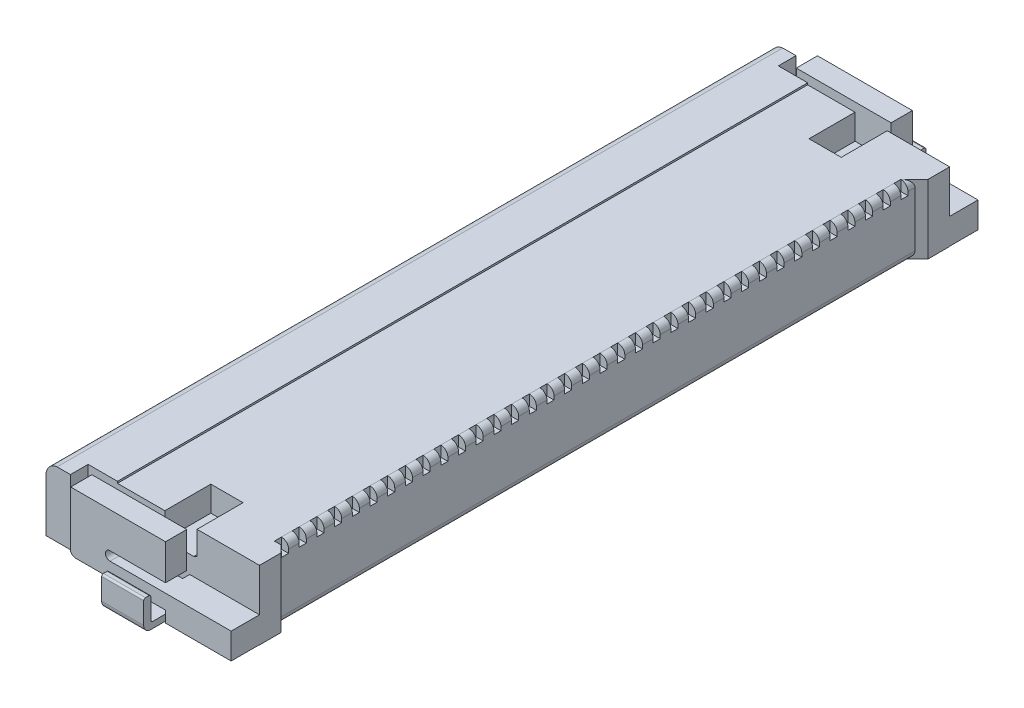
SolidWorks part; units mm, degrees
ref_plane "Front Plane" through (0, 0, 0) normal (0, 0, 1) x (1, 0, 0)
ref_plane "Top Plane" through (0, 0, 0) normal (0, 1, 0) x (1, 0, 0)
ref_plane "Right Plane" through (0, 0, 0) normal (1, 0, 0) x (0, 0, -1)
sketch "Sketch5" plane through (0, 0, 0) normal (0, 0, 1) x (1, 0, 0)
  line L0 (40.6667, 46) -> (203.3333, 46) construction
  line L1 (1.0365, 0.0671) -> (5.5705, 0.0671)
  line L2 (5.5705, 0.0671) -> (5.5705, 2.0592)
  line L3 (5.5705, 2.0592) -> (1.0365, 2.0592)
  line L4 (1.0365, 2.0592) -> (1.0365, 0.0671)
  line L5 (1.0365, 0.9096) -> (0.7294, 0.9096)
  line L6 (0.7294, 0.9096) -> (0.7294, 2.0592)
  line L7 (0.7294, 2.0592) -> (1.0365, 2.0592)
  line L8 (2.4126, 0.8573) -> (2.4126, 0.0671)
  line L9 (2.4126, 0.8573) -> (3.5997, 0.8573)
  line L10 (3.5997, 0.8573) -> (3.5997, 0.0671)
  line L11 (3.5997, 0.7994) -> (5.5705, 0.7994)
  line L12 (2.4126, 0.7994) -> (2.1463, 0.7994)
  line L13 (2.1463, 1.0542) -> (3.7156, 1.0542)
  line L14 (3.7156, 1.0542) -> (3.7156, 2.0592)
  line L15 (2.4126, 0.175) -> (1.0365, 0.175)
  line L16 (3.5997, 0.175) -> (5.5705, 0.175)
  line L17 (2.4126, 0.3858) -> (1.1847, 0.3858)
  line L18 (0.0415, 1.6702) -> (0.0415, 0.2199)
  line L19 (0.0415, 0.2199) -> (0.7294, 0.2199)
  line L20 (0.7294, 0.2199) -> (0.7294, 0.9096)
  line L21 (0.7294, 2.0592) -> (0.3527, 2.0592)
  line L22 (3.8064, 2.0592) -> (3.8064, 1.3482)
  line L23 (3.8064, 1.3482) -> (3.7156, 1.2979)
  line L24 (0.9408, 0.9096) -> (0.9408, 1.2134)
  line L25 (0.9408, 1.2134) -> (1.0365, 1.2134)
  line L26 (3.5997, 0.3858) -> (3.7156, 0.3858)
  line L27 (3.7156, 0.3858) -> (3.7156, 0.175)
  arc A0 (2.1463, 0.7994) -> (2.1463, 1.0542) centre (2.1463, 0.9268) cw
  arc A1 (0.0415, 1.6702) -> (0.3527, 2.0592) centre (0.3916, 1.7091) cw
  spline S0 degree 2 poles (1.1847, 0.3858) (1.082, 0.3886) (1.0365, 0.477) knots 0 0 0 1 1 1
extrude "Boss-Extrude1" add sketch "Sketch5" against normal blind 0.6 contours S0 L17 L8 L12 A0 L13 L14 L3 L4
sketch "Sketch7" plane through (0, 0, 0) normal (0, 0, 1) x (1, 0, 0)
  line L0 (5.5705, 0.0671) -> (5.5705, 2.0592) construction
  line L2 (3.7156, 0.3858) -> (3.7156, 0.175) construction
  line L3 (3.5997, 0.3858) -> (3.7156, 0.3858) construction
  line L4 (3.5997, 0.7994) -> (5.5705, 0.7994) construction
  line L10 (5.5705, 0.175) -> (5.5705, 0.7994)
  line L11 (3.7156, 0.175) -> (3.7156, 0.0671)
  line L12 (3.7156, 0.3858) -> (3.7156, 0.175)
  line L13 (3.5997, 0.3858) -> (3.7156, 0.3858)
  line L14 (3.5997, 0.7994) -> (5.5705, 0.7994)
  line L15 (3.5997, 0.7994) -> (3.5997, 0.3858)
  line L16 (1.0365, 0.0671) -> (5.5705, 0.0671) construction
  line L17 (3.7156, 0.0671) -> (5.5705, 0.0671)
  line L18 (5.5705, 0.0671) -> (5.5705, 0.175)
  line L20 (2.4126, 0.3858) -> (3.5997, 0.3858)
  line L21 (2.4126, 0.7994) -> (3.5997, 0.7994)
  line L24 (2.4126, 0.7994) -> (2.4126, 0.3858)
extrude "Boss-Extrude2" add sketch "Sketch7" against normal blind 0.8 separate body contours L17 L18 L10 L14 L15 L13 L12 L11
sketch "Sketch8" plane through (0, 0, 0) normal (0, 0, 1) x (1, 0, 0)
  line L0 (3.5997, 0.7994) -> (2.4126, 0.7994)
  line L1 (3.5997, 0.3858) -> (2.4126, 0.3858)
  line L2 (3.5997, 0.8573) -> (3.5997, 0.0671) construction
  line L3 (2.4126, 0.8573) -> (2.4126, 0.0671) construction
  line L4 (3.5997, 0.7994) -> (3.5997, 0.3858)
  line L5 (2.4126, 0.7994) -> (2.4126, 0.3858)
extrude "Boss-Extrude3" add sketch "Sketch8" against normal blind 0.6
sketch "Sketch11" plane through (0, 0, 0) normal (0, 1, 0) x (1, 0, 0)
  line L0 (5.5705, 0.8) -> (5.5705, 1.4131)
  line L1 (5.5705, 1.4131) -> (5.3077, 1.5403)
  line L2 (5.3077, 1.5403) -> (5.3077, 9.05)
  line L3 (3.5997, 0) -> (5.5705, 0) construction
  line L4 (5.3077, 9.05) -> (1.7077, 9.05)
  line L5 (1.7077, 9.05) -> (1.7077, 0.8)
  line L6 (1.7077, 0.8) -> (5.5705, 0.8)
  dimension "D1" = 9.05
  dimension "D2" = 3.6
ref_plane "Plane1" through (0, 0.06, 0) normal (0, 1, 0) x (1, 0, 0)
sketch "Sketch13" plane through (0, 0.06, 0) normal (0, 1, 0) x (1, 0, 0)
  line L0 (3.7156, 0) -> (1.0365, 0) construction
  line L2 (5.5705, 0.8) -> (5.5705, 1.4131) construction
  line L6 (5.3077, 10.55) -> (1.6924, 10.55)
  line L7 (5.5705, 1.4131) -> (5.3881, 1.5955)
  line L8 (5.5705, 0.8) -> (5.5705, 1.4131)
  line L9 (1.6924, 10.55) -> (1.6924, 0.8)
  line L10 (5.3881, 1.5955) -> (5.3881, 10.55)
  line L11 (1.6924, 0.8) -> (5.5705, 0.8)
  line L12 (5.3881, 10.55) -> (5.3077, 10.55)
  dimension "D1" = 10.55
extrude "Boss-Extrude5" add sketch "Sketch13" along normal up to surface (1.9992 mm away) up to face at (2.376, 2.0592, -0.3)
sketch "Sketch17" plane through (0, 0, -0.8) normal (0, 0, 1) x (1, 0, 0)
  line L0 (3.8064, 1.3482) -> (3.7156, 1.2979) construction
  line L1 (3.8064, 2.0592) -> (3.8064, 1.3482) construction
  line L2 (3.8064, 1.3482) -> (3.7156, 1.2979)
  line L3 (3.8064, 2.0592) -> (3.8064, 1.3482)
  line L4 (3.7156, 1.2979) -> (2.8963, 1.2979)
  line L5 (2.8963, 1.2979) -> (2.8963, 2.0592)
  line L6 (1.6924, 2.0592) -> (5.5705, 2.0592) construction
  line L7 (2.8963, 2.0592) -> (3.8064, 2.0592)
extrude "Cut-Extrude6" cut sketch "Sketch17" against normal blind 1.3
sketch "Sketch18" plane through (0, 0, -0.8) normal (0, 0, 1) x (1, 0, 0)
  line L0 (0.0415, 1.6702) -> (0.0415, 0.2199)
  line L1 (0.7294, 2.0592) -> (0.7294, 0.9096)
  line L5 (0.0415, 0.2199) -> (0.7294, 0.2199) construction
  line L6 (0.7294, 0.2199) -> (0.7294, 0.9096) construction
  line L9 (0.7294, 2.0592) -> (0.3527, 2.0592) construction
  line L15 (0.0415, 0.2199) -> (0.7294, 0.2199)
  line L16 (0.7294, 0.2199) -> (0.7294, 0.9096)
  line L19 (0.7294, 2.0592) -> (0.3527, 2.0592)
  arc A0 (0.3527, 2.0592) -> (0.0415, 1.6702) centre (0.3916, 1.7091) ccw construction
  arc A1 (0.3527, 2.0592) -> (0.0415, 1.6702) centre (0.3916, 1.7091) ccw
sketch "Sketch19" plane through (1.6924, 0, 0) normal (-1, 0, 0) x (0, 0, 1)
  line L0 (-10.55, 2.0592) -> (-0.8, 2.0592) construction
  line L1 (-10.55, 2.0592) -> (-0.8, 2.0592)
  line L4 (-0.8, 2.0592) -> (-10.55, 2.0592)
  line L5 (-10.55, 2.0592) -> (-10.55, 0.06)
  line L6 (-10.55, 0.06) -> (-0.8, 0.06)
  line L7 (-0.8, 0.06) -> (-0.8, 2.0592)
  line L9 (-10.55, 2.0592) -> (-10.55, 0.06)
  line L10 (-10.55, 0.06) -> (-0.8, 0.06)
  line L11 (-0.8, 0.06) -> (-0.8, 2.0592)
  dimension "D1" = 0
extrude "Boss-Extrude6" add sketch "Sketch19" along normal up to vertex (0.963 mm away) separate body up to point (0.7294, 2.0592, -0.8)
extrude "Boss-Extrude7" add sketch "Sketch18" against normal up to surface (9.75 mm away) up to face at (3.5403, 1.0596, -10.55)
sketch "Sketch20" plane through (0, 0, -0.8) normal (0, 0, 1) x (1, 0, 0)
  line L0 (1.0365, 2.0592) -> (1.0365, 0.0671) construction
  line L1 (0.7294, 0.2199) -> (0.7294, 0.9096) construction
  line L2 (1.0365, 0.9096) -> (0.7294, 0.9096) construction
  line L3 (1.0365, 2.0592) -> (1.0365, 0.0671)
  line L4 (0.7294, 0.2199) -> (0.7294, 0.9096)
  line L5 (1.0365, 0.9096) -> (0.7294, 0.9096)
  line L6 (0.7294, 0.2199) -> (0.7294, 0.06)
  line L7 (0.7294, -0.0203) -> (1.0365, -0.0203)
  line L8 (1.0365, -0.0203) -> (1.0365, 0.0671)
  line L9 (0.7294, 0.06) -> (0.7294, -0.0203)
extrude "Cut-Extrude7" cut sketch "Sketch20" against normal up to surface (9.75 mm away)
sketch "Sketch21" plane through (0, 0, -0.8) normal (0, 0, 1) x (1, 0, 0)
  line L0 (0.7294, 0.2199) -> (0.7294, 0.9096) construction
  line L1 (0.0415, 0.2199) -> (0.7294, 0.2199) construction
  line L2 (0.0415, 1.6702) -> (0.0415, 0.2199) construction
  line L3 (0.7294, 2.0592) -> (0.3527, 2.0592) construction
  line L4 (0.7294, 0.9096) -> (0.7294, 2.0592) construction
  line L5 (0.7294, 0.2199) -> (0.7294, 0.9096)
  line L6 (0.0415, 0.2199) -> (0.7294, 0.2199)
  line L7 (0.0415, 1.6702) -> (0.0415, 0.2199)
  line L8 (0.7294, 2.0592) -> (0.3527, 2.0592)
  line L9 (0.7294, 0.9096) -> (0.7294, 2.0592)
  arc A0 (0.3527, 2.0592) -> (0.0415, 1.6702) centre (0.3916, 1.7091) ccw construction
  arc A1 (0.3527, 2.0592) -> (0.0415, 1.6702) centre (0.3916, 1.7091) ccw
extrude "Boss-Extrude8" add sketch "Sketch21" along normal blind 0.5
mirror "Mirror1" of "Boss-Extrude8", "Cut-Extrude7", "Boss-Extrude7", "Boss-Extrude6", "Cut-Extrude6", "Boss-Extrude5", "Boss-Extrude3", "Boss-Extrude2", "Boss-Extrude1"
sketch "Sketch22" plane through (0, 2.0592, 0) normal (0, 1, 0) x (1, 0, 0)
  line L0 (1.5582, 20.3) -> (1.5582, 0.8)
  line L20 (2.8963, 19) -> (2.8963, 20.3)
  line L21 (2.8963, 20.3) -> (0.7294, 20.3)
  line L22 (0.7294, 20.3) -> (0.7294, 20.8)
  line L23 (0.7294, 20.8) -> (0.3527, 20.8)
  line L24 (0.3527, 20.8) -> (0.3527, 0.3)
  line L25 (0.3527, 0.3) -> (0.7294, 0.3)
  line L26 (0.7294, 0.3) -> (0.7294, 0.8)
  line L27 (0.7294, 0.8) -> (2.8963, 0.8)
  line L28 (2.8963, 0.8) -> (2.8963, 2.1)
  line L29 (2.8963, 2.1) -> (3.8064, 2.1)
  line L30 (3.8064, 2.1) -> (3.8064, 0.8)
  line L31 (3.8064, 0.8) -> (5.5705, 0.8)
  line L32 (5.5705, 0.8) -> (5.5705, 1.4131)
  line L33 (5.5705, 1.4131) -> (5.3881, 1.5955)
  line L34 (5.5705, 1.4131) -> (5.3881, 1.5955)
  line L35 (5.3881, 1.5955) -> (5.3881, 19.5045)
  line L36 (5.5705, 19.6869) -> (5.5705, 20.3)
  line L37 (5.5705, 20.3) -> (3.8064, 20.3)
  line L38 (3.8064, 20.3) -> (3.8064, 19)
  line L39 (3.8064, 19) -> (2.8963, 19)
  line L40 (2.8963, 19) -> (2.8963, 20.3)
  line L41 (2.8963, 20.3) -> (1.5582, 20.3)
  line L43 (5.3881, 1.5955) -> (5.3881, 19.5045)
  line L44 (5.3881, 19.5045) -> (5.5705, 19.6869)
  line L45 (5.3881, 19.5045) -> (5.5705, 19.6869)
  line L46 (0.7294, 0.3) -> (0.7294, 0.8)
  line L47 (1.5582, 0.8) -> (2.8963, 0.8)
  line L48 (2.8963, 0.8) -> (2.8963, 2.1)
  line L49 (2.8963, 2.1) -> (3.8064, 2.1)
  line L50 (3.8064, 2.1) -> (3.8064, 0.8)
  line L51 (3.8064, 0.8) -> (5.5705, 0.8)
  line L52 (5.5705, 0.8) -> (5.5705, 1.4131)
  line L56 (5.5705, 19.6869) -> (5.5705, 20.3)
  line L57 (5.5705, 20.3) -> (3.8064, 20.3)
  line L58 (3.8064, 20.3) -> (3.8064, 19)
  line L59 (3.8064, 19) -> (2.8963, 19)
  dimension "D1" = 0
extrude "Cut-Extrude8" cut sketch "Sketch22" against normal blind 0.05
fillet "Fillet4" radius 0.2 2 edges at (5.3881, 2.0092, -10.55) (5.3881, 0.06, -10.55)
sketch "Sketch26" plane through (0, 0, 0) normal (0, 0, 1) x (1, 0, 0)
  line L1 (3.5997, 0.8573) -> (3.5997, 0.0671) construction
  line L2 (2.4126, 0.8573) -> (2.4126, 0.0671) construction
  line L3 (2.4126, 0.8573) -> (3.5997, 0.8573) construction
  line L4 (2.4126, 0.0671) -> (2.4126, 0)
  line L5 (3.5997, 0.8573) -> (3.5997, 0.0671)
  line L6 (2.4126, 0.8573) -> (2.4126, 0.0671)
  line L7 (2.4126, 0.8573) -> (3.5997, 0.8573)
  line L8 (2.4126, 0) -> (3.5997, 0)
  line L9 (3.5997, 0) -> (3.5997, 0.0671)
  line L10 (2.4126, 0.175) -> (3.5997, 0.175)
extrude "Boss-Extrude9" add sketch "Sketch26" along normal blind 0.5 contours L10 L6 L4 L8 L9 L5
sketch "Sketch27" plane through (0, 0, 0.5) normal (0, 0, 1) x (1, 0, 0)
  line L0 (2.4126, 0.175) -> (3.5997, 0.175) construction
  line L1 (3.5997, 0.8573) -> (3.5997, 0.0671) construction
  line L2 (2.4126, 0.8573) -> (2.4126, 0.0671) construction
  line L3 (2.4126, 0.8573) -> (3.5997, 0.8573) construction
  line L4 (2.4126, 0.175) -> (3.5997, 0.175)
  line L5 (3.5997, 0.8573) -> (3.5997, 0.175)
  line L6 (2.4126, 0.8573) -> (2.4126, 0.175)
  line L7 (2.4126, 0.8573) -> (3.5997, 0.8573)
extrude "Boss-Extrude10" add sketch "Sketch27" against normal blind 0.2
fillet "Fillet6" radius 0.2 1 edges at (3.0062, 0, 0.5)
fillet "Fillet7" radius 0.05 2 edges at (3.0062, 0.8573, 0.5) (3.0062, 0.8573, 0.3)
sketch "Sketch28" plane through (2.4126, 0, 0) normal (-1, 0, 0) x (0, 0, 1)
  line L0 (-0.8, 0.3858) -> (-0.8, 0.0671) construction
  line L1 (-0.8, 0.3233) -> (-0.8, 0.1393)
  line L2 (0, 0.175) -> (-0.5527, 0.175)
  line L3 (0, 0) -> (-0.5527, 0)
  line L4 (0, 0.175) -> (0, 0)
  arc A0 (-0.5527, 0) -> (-0.8, 0.1393) centre (-0.5056, 0.3729) cw
  arc A1 (-0.5527, 0.175) -> (-0.8, 0.3233) centre (-0.4668, 0.5985) cw
extrude "Boss-Extrude11" add sketch "Sketch28" against normal up to surface (1.1871 mm away) up to face at (3.5997, 0.4287, 0.3046)
ref_plane "Plane3" through (0, 0, -10.55) normal (0, 0, 1) x (1, 0, 0)
mirror "Mirror6" about plane through (0, 0, -10.55) normal (0, 0, 1) of "Boss-Extrude11", "Fillet7", "Fillet6", "Boss-Extrude10", "Boss-Extrude9"
fillet "Fillet8" radius 0.05 1 edges at (3.0062, 0.175, 0.3)
fillet "Fillet9" radius 0.05 1 edges at (3.0062, 0.175, -21.4)
sketch "Sketch29" plane through (0, 2.0092, 0) normal (0, 1, 0) x (1, 0, 0)
  line L0 (6.2655, 18.8045) -> (6.2655, 18.6045)
  line L1 (5.1881, 19.3045) -> (6.2655, 19.3045)
  line L2 (5.1881, 19.3045) -> (5.1881, 19.1045)
  line L3 (5.1881, 19.1045) -> (6.2655, 19.1045)
  line L4 (6.2655, 19.3045) -> (6.2655, 19.1045)
  line L5 (5.1881, 18.8045) -> (6.2655, 18.8045)
  line L6 (5.1881, 18.6045) -> (6.2655, 18.6045)
  line L7 (5.1881, 18.8045) -> (5.1881, 18.6045)
  line L8 (6.2655, 18.3045) -> (6.2655, 18.1045)
  line L9 (5.1881, 18.3045) -> (6.2655, 18.3045)
  line L10 (5.1881, 18.1045) -> (6.2655, 18.1045)
  line L11 (5.1881, 18.3045) -> (5.1881, 18.1045)
  line L12 (6.2655, 17.8045) -> (6.2655, 17.6045)
  line L13 (5.1881, 17.8045) -> (6.2655, 17.8045)
  line L14 (5.1881, 17.6045) -> (6.2655, 17.6045)
  line L15 (5.1881, 17.8045) -> (5.1881, 17.6045)
  line L16 (6.2655, 17.3045) -> (6.2655, 17.1045)
  line L17 (5.1881, 17.3045) -> (6.2655, 17.3045)
  line L18 (5.1881, 17.1045) -> (6.2655, 17.1045)
  line L19 (5.1881, 17.3045) -> (5.1881, 17.1045)
  line L20 (6.2655, 16.8045) -> (6.2655, 16.6045)
  line L21 (5.1881, 16.8045) -> (6.2655, 16.8045)
  line L22 (5.1881, 16.6045) -> (6.2655, 16.6045)
  line L23 (5.1881, 16.8045) -> (5.1881, 16.6045)
  line L24 (6.2655, 16.3045) -> (6.2655, 16.1045)
  line L25 (5.1881, 16.3045) -> (6.2655, 16.3045)
  line L26 (5.1881, 16.1045) -> (6.2655, 16.1045)
  line L27 (5.1881, 16.3045) -> (5.1881, 16.1045)
  line L28 (6.2655, 15.8045) -> (6.2655, 15.6045)
  line L29 (5.1881, 15.8045) -> (6.2655, 15.8045)
  line L30 (5.1881, 15.6045) -> (6.2655, 15.6045)
  line L31 (5.1881, 15.8045) -> (5.1881, 15.6045)
  line L32 (6.2655, 15.3045) -> (6.2655, 15.1045)
  line L33 (5.1881, 15.3045) -> (6.2655, 15.3045)
  line L34 (5.1881, 15.1045) -> (6.2655, 15.1045)
  line L35 (5.1881, 15.3045) -> (5.1881, 15.1045)
  line L36 (6.2655, 14.8045) -> (6.2655, 14.6045)
  line L37 (5.1881, 14.8045) -> (6.2655, 14.8045)
  line L38 (5.1881, 14.6045) -> (6.2655, 14.6045)
  line L39 (5.1881, 14.8045) -> (5.1881, 14.6045)
  line L40 (6.2655, 14.3045) -> (6.2655, 14.1045)
  line L41 (5.1881, 14.3045) -> (6.2655, 14.3045)
  line L42 (5.1881, 14.1045) -> (6.2655, 14.1045)
  line L43 (5.1881, 14.3045) -> (5.1881, 14.1045)
  line L44 (6.2655, 13.8045) -> (6.2655, 13.6045)
  line L45 (5.1881, 13.8045) -> (6.2655, 13.8045)
  line L46 (5.1881, 13.6045) -> (6.2655, 13.6045)
  line L47 (5.1881, 13.8045) -> (5.1881, 13.6045)
  line L48 (6.2655, 13.3045) -> (6.2655, 13.1045)
  line L49 (5.1881, 13.3045) -> (6.2655, 13.3045)
  line L50 (5.1881, 13.1045) -> (6.2655, 13.1045)
  line L51 (5.1881, 13.3045) -> (5.1881, 13.1045)
  line L52 (6.2655, 12.8045) -> (6.2655, 12.6045)
  line L53 (5.1881, 12.8045) -> (6.2655, 12.8045)
  line L54 (5.1881, 12.6045) -> (6.2655, 12.6045)
  line L55 (5.1881, 12.8045) -> (5.1881, 12.6045)
  line L56 (6.2655, 12.3045) -> (6.2655, 12.1045)
  line L57 (5.1881, 12.3045) -> (6.2655, 12.3045)
  line L58 (5.1881, 12.1045) -> (6.2655, 12.1045)
  line L59 (5.1881, 12.3045) -> (5.1881, 12.1045)
  line L60 (6.2655, 11.8045) -> (6.2655, 11.6045)
  line L61 (5.1881, 11.8045) -> (6.2655, 11.8045)
  line L62 (5.1881, 11.6045) -> (6.2655, 11.6045)
  line L63 (5.1881, 11.8045) -> (5.1881, 11.6045)
  line L64 (6.2655, 11.3045) -> (6.2655, 11.1045)
  line L65 (5.1881, 11.3045) -> (6.2655, 11.3045)
  line L66 (5.1881, 11.1045) -> (6.2655, 11.1045)
  line L67 (5.1881, 11.3045) -> (5.1881, 11.1045)
  line L68 (6.2655, 10.8045) -> (6.2655, 10.6045)
  line L69 (5.1881, 10.8045) -> (6.2655, 10.8045)
  line L70 (5.1881, 10.6045) -> (6.2655, 10.6045)
  line L71 (5.1881, 10.8045) -> (5.1881, 10.6045)
  line L72 (6.2655, 10.3045) -> (6.2655, 10.1045)
  line L73 (5.1881, 10.3045) -> (6.2655, 10.3045)
  line L74 (5.1881, 10.1045) -> (6.2655, 10.1045)
  line L75 (5.1881, 10.3045) -> (5.1881, 10.1045)
  line L76 (6.2655, 9.8045) -> (6.2655, 9.6045)
  line L77 (5.1881, 9.8045) -> (6.2655, 9.8045)
  line L78 (5.1881, 9.6045) -> (6.2655, 9.6045)
  line L79 (5.1881, 9.8045) -> (5.1881, 9.6045)
  line L80 (6.2655, 9.3045) -> (6.2655, 9.1045)
  line L81 (5.1881, 9.3045) -> (6.2655, 9.3045)
  line L82 (5.1881, 9.1045) -> (6.2655, 9.1045)
  line L83 (5.1881, 9.3045) -> (5.1881, 9.1045)
  line L84 (6.2655, 8.8045) -> (6.2655, 8.6045)
  line L85 (5.1881, 8.8045) -> (6.2655, 8.8045)
  line L86 (5.1881, 8.6045) -> (6.2655, 8.6045)
  line L87 (5.1881, 8.8045) -> (5.1881, 8.6045)
  line L88 (6.2655, 8.3045) -> (6.2655, 8.1045)
  line L89 (5.1881, 8.3045) -> (6.2655, 8.3045)
  line L90 (5.1881, 8.1045) -> (6.2655, 8.1045)
  line L91 (5.1881, 8.3045) -> (5.1881, 8.1045)
  line L92 (6.2655, 7.8045) -> (6.2655, 7.6045)
  line L93 (5.1881, 7.8045) -> (6.2655, 7.8045)
  line L94 (5.1881, 7.6045) -> (6.2655, 7.6045)
  line L95 (5.1881, 7.8045) -> (5.1881, 7.6045)
  line L96 (6.2655, 7.3045) -> (6.2655, 7.1045)
  line L97 (5.1881, 7.3045) -> (6.2655, 7.3045)
  line L98 (5.1881, 7.1045) -> (6.2655, 7.1045)
  line L99 (5.1881, 7.3045) -> (5.1881, 7.1045)
  line L100 (6.2655, 6.8045) -> (6.2655, 6.6045)
  line L101 (5.1881, 6.8045) -> (6.2655, 6.8045)
  line L102 (5.1881, 6.6045) -> (6.2655, 6.6045)
  line L103 (5.1881, 6.8045) -> (5.1881, 6.6045)
  line L104 (6.2655, 6.3045) -> (6.2655, 6.1045)
  line L105 (5.1881, 6.3045) -> (6.2655, 6.3045)
  line L106 (5.1881, 6.1045) -> (6.2655, 6.1045)
  line L107 (5.1881, 6.3045) -> (5.1881, 6.1045)
  line L108 (6.2655, 5.8045) -> (6.2655, 5.6045)
  line L109 (5.1881, 5.8045) -> (6.2655, 5.8045)
  line L110 (5.1881, 5.6045) -> (6.2655, 5.6045)
  line L111 (5.1881, 5.8045) -> (5.1881, 5.6045)
  line L112 (6.2655, 5.3045) -> (6.2655, 5.1045)
  line L113 (5.1881, 5.3045) -> (6.2655, 5.3045)
  line L114 (5.1881, 5.1045) -> (6.2655, 5.1045)
  line L115 (5.1881, 5.3045) -> (5.1881, 5.1045)
  line L116 (6.2655, 4.8045) -> (6.2655, 4.6045)
  line L117 (5.1881, 4.8045) -> (6.2655, 4.8045)
  line L118 (5.1881, 4.6045) -> (6.2655, 4.6045)
  line L119 (5.1881, 4.8045) -> (5.1881, 4.6045)
  line L120 (6.2655, 4.3045) -> (6.2655, 4.1045)
  line L121 (5.1881, 4.3045) -> (6.2655, 4.3045)
  line L122 (5.1881, 4.1045) -> (6.2655, 4.1045)
  line L123 (5.1881, 4.3045) -> (5.1881, 4.1045)
  line L124 (6.2655, 3.8045) -> (6.2655, 3.6045)
  line L125 (5.1881, 3.8045) -> (6.2655, 3.8045)
  line L126 (5.1881, 3.6045) -> (6.2655, 3.6045)
  line L127 (5.1881, 3.8045) -> (5.1881, 3.6045)
  line L128 (6.2655, 3.3045) -> (6.2655, 3.1045)
  line L129 (5.1881, 3.3045) -> (6.2655, 3.3045)
  line L130 (5.1881, 3.1045) -> (6.2655, 3.1045)
  line L131 (5.1881, 3.3045) -> (5.1881, 3.1045)
  line L132 (6.2655, 2.8045) -> (6.2655, 2.6045)
  line L133 (5.1881, 2.8045) -> (6.2655, 2.8045)
  line L134 (5.1881, 2.6045) -> (6.2655, 2.6045)
  line L135 (5.1881, 2.8045) -> (5.1881, 2.6045)
  line L136 (6.2655, 2.3045) -> (6.2655, 2.1045)
  line L137 (5.1881, 2.3045) -> (6.2655, 2.3045)
  line L138 (5.1881, 2.1045) -> (6.2655, 2.1045)
  line L139 (5.1881, 2.3045) -> (5.1881, 2.1045)
  line L140 (6.2655, 1.8045) -> (6.2655, 1.6045)
  line L141 (5.1881, 1.8045) -> (6.2655, 1.8045)
  line L142 (5.1881, 1.6045) -> (6.2655, 1.6045)
  line L143 (5.1881, 1.8045) -> (5.1881, 1.6045)
  dimension "D1" = 0.2
  dimension "D2" = 36
extrude "Cut-Extrude9" cut sketch "Sketch29" against normal blind 0.3
sketch "Sketch30" plane through (0.0415, 0, 0) normal (-1, 0, 0) x (0, 0, 1)
  line L0 (-19.835, 0.2199) -> (-19.835, 0.9096)
  line L1 (-20.8, 0.2199) -> (-0.3, 0.2199) construction
  line L2 (-19.835, 0.9096) -> (-18.505, 0.9096)
  line L3 (-18.505, 0.9096) -> (-18.505, 1.2296)
  line L4 (-18.505, 1.2296) -> (-2.595, 1.2296)
  line L5 (-10.55, 5.4524) -> (-10.55, -3.5074) construction
  line L6 (-20.3, 0.9096) -> (-0.8, 0.9096) construction
  line L7 (-19.835, 0.9096) -> (-18.505, 0.9096)
  line L8 (-1.265, 0.2199) -> (-1.265, 0.9096)
  line L9 (-1.265, 0.9096) -> (-2.595, 0.9096)
  line L10 (-2.595, 0.9096) -> (-2.595, 1.2296)
  line L11 (-19.835, 0.2199) -> (-1.265, 0.2199)
  point P15 (-10.55, 1.2296)
  line M7 (-20.8, 0.2199) -> (-0.3, 0.2199)
  dimension "D1" = 9.285
  dimension "D2" = 1.33
  dimension "D3" = 0.32
extrude "Cut-Extrude10" cut sketch "Sketch30" against normal up to surface (0.688 mm away) contours L5 L4 L3 L2 L0 M7 | L4 L5 L11 L8 L9 L10 up to face at (0.7294, 1.312, -10.55)
sketch "Sketch31" plane through (1.0365, 0, 0) normal (-1, 0, 0) x (0, 0, 1)
  line L0 (-20.3, 0.9096) -> (-0.8, 0.9096) construction
  line L1 (-19.385, 0.9096) -> (-19.185, 0.9096)
  line L2 (-19.835, 0.2199) -> (-19.835, 0.9096) construction
  line L3 (-19.385, 0.9096) -> (-19.185, 0.9096)
  line L4 (-19.385, 0.9096) -> (-19.385, 0.3696)
  line L5 (-19.385, 0.3696) -> (-19.185, 0.3696)
  line L6 (-19.185, 0.9096) -> (-19.185, 0.3696)
  line L7 (-18.885, 0.9096) -> (-18.685, 0.9096)
  line L8 (-18.685, 0.9096) -> (-18.685, 0.3696)
  line L9 (-18.885, 0.9096) -> (-18.885, 0.3696)
  line L10 (-18.885, 0.3696) -> (-18.685, 0.3696)
  line L11 (-18.385, 0.9096) -> (-18.185, 0.9096)
  line L12 (-18.185, 0.9096) -> (-18.185, 0.3696)
  line L13 (-18.385, 0.9096) -> (-18.385, 0.3696)
  line L14 (-18.385, 0.3696) -> (-18.185, 0.3696)
  line L15 (-17.885, 0.9096) -> (-17.685, 0.9096)
  line L16 (-17.685, 0.9096) -> (-17.685, 0.3696)
  line L17 (-17.885, 0.9096) -> (-17.885, 0.3696)
  line L18 (-17.885, 0.3696) -> (-17.685, 0.3696)
  line L19 (-17.385, 0.9096) -> (-17.185, 0.9096)
  line L20 (-17.185, 0.9096) -> (-17.185, 0.3696)
  line L21 (-17.385, 0.9096) -> (-17.385, 0.3696)
  line L22 (-17.385, 0.3696) -> (-17.185, 0.3696)
  line L23 (-16.885, 0.9096) -> (-16.685, 0.9096)
  line L24 (-16.685, 0.9096) -> (-16.685, 0.3696)
  line L25 (-16.885, 0.9096) -> (-16.885, 0.3696)
  line L26 (-16.885, 0.3696) -> (-16.685, 0.3696)
  line L27 (-16.385, 0.9096) -> (-16.185, 0.9096)
  line L28 (-16.185, 0.9096) -> (-16.185, 0.3696)
  line L29 (-16.385, 0.9096) -> (-16.385, 0.3696)
  line L30 (-16.385, 0.3696) -> (-16.185, 0.3696)
  line L31 (-15.885, 0.9096) -> (-15.685, 0.9096)
  line L32 (-15.685, 0.9096) -> (-15.685, 0.3696)
  line L33 (-15.885, 0.9096) -> (-15.885, 0.3696)
  line L34 (-15.885, 0.3696) -> (-15.685, 0.3696)
  line L35 (-15.385, 0.9096) -> (-15.185, 0.9096)
  line L36 (-15.185, 0.9096) -> (-15.185, 0.3696)
  line L37 (-15.385, 0.9096) -> (-15.385, 0.3696)
  line L38 (-15.385, 0.3696) -> (-15.185, 0.3696)
  line L39 (-14.885, 0.9096) -> (-14.685, 0.9096)
  line L40 (-14.685, 0.9096) -> (-14.685, 0.3696)
  line L41 (-14.885, 0.9096) -> (-14.885, 0.3696)
  line L42 (-14.885, 0.3696) -> (-14.685, 0.3696)
  line L43 (-14.385, 0.9096) -> (-14.185, 0.9096)
  line L44 (-14.185, 0.9096) -> (-14.185, 0.3696)
  line L45 (-14.385, 0.9096) -> (-14.385, 0.3696)
  line L46 (-14.385, 0.3696) -> (-14.185, 0.3696)
  line L47 (-13.885, 0.9096) -> (-13.685, 0.9096)
  line L48 (-13.685, 0.9096) -> (-13.685, 0.3696)
  line L49 (-13.885, 0.9096) -> (-13.885, 0.3696)
  line L50 (-13.885, 0.3696) -> (-13.685, 0.3696)
  line L51 (-13.385, 0.9096) -> (-13.185, 0.9096)
  line L52 (-13.185, 0.9096) -> (-13.185, 0.3696)
  line L53 (-13.385, 0.9096) -> (-13.385, 0.3696)
  line L54 (-13.385, 0.3696) -> (-13.185, 0.3696)
  line L55 (-12.885, 0.9096) -> (-12.685, 0.9096)
  line L56 (-12.685, 0.9096) -> (-12.685, 0.3696)
  line L57 (-12.885, 0.9096) -> (-12.885, 0.3696)
  line L58 (-12.885, 0.3696) -> (-12.685, 0.3696)
  line L59 (-12.385, 0.9096) -> (-12.185, 0.9096)
  line L60 (-12.185, 0.9096) -> (-12.185, 0.3696)
  line L61 (-12.385, 0.9096) -> (-12.385, 0.3696)
  line L62 (-12.385, 0.3696) -> (-12.185, 0.3696)
  line L63 (-11.885, 0.9096) -> (-11.685, 0.9096)
  line L64 (-11.685, 0.9096) -> (-11.685, 0.3696)
  line L65 (-11.885, 0.9096) -> (-11.885, 0.3696)
  line L66 (-11.885, 0.3696) -> (-11.685, 0.3696)
  line L67 (-11.385, 0.9096) -> (-11.185, 0.9096)
  line L68 (-11.185, 0.9096) -> (-11.185, 0.3696)
  line L69 (-11.385, 0.9096) -> (-11.385, 0.3696)
  line L70 (-11.385, 0.3696) -> (-11.185, 0.3696)
  line L71 (-10.885, 0.9096) -> (-10.685, 0.9096)
  line L72 (-10.685, 0.9096) -> (-10.685, 0.3696)
  line L73 (-10.885, 0.9096) -> (-10.885, 0.3696)
  line L74 (-10.885, 0.3696) -> (-10.685, 0.3696)
  line L75 (-10.385, 0.9096) -> (-10.185, 0.9096)
  line L76 (-10.185, 0.9096) -> (-10.185, 0.3696)
  line L77 (-10.385, 0.9096) -> (-10.385, 0.3696)
  line L78 (-10.385, 0.3696) -> (-10.185, 0.3696)
  line L79 (-9.885, 0.9096) -> (-9.685, 0.9096)
  line L80 (-9.685, 0.9096) -> (-9.685, 0.3696)
  line L81 (-9.885, 0.9096) -> (-9.885, 0.3696)
  line L82 (-9.885, 0.3696) -> (-9.685, 0.3696)
  line L83 (-9.385, 0.9096) -> (-9.185, 0.9096)
  line L84 (-9.185, 0.9096) -> (-9.185, 0.3696)
  line L85 (-9.385, 0.9096) -> (-9.385, 0.3696)
  line L86 (-9.385, 0.3696) -> (-9.185, 0.3696)
  line L87 (-8.885, 0.9096) -> (-8.685, 0.9096)
  line L88 (-8.685, 0.9096) -> (-8.685, 0.3696)
  line L89 (-8.885, 0.9096) -> (-8.885, 0.3696)
  line L90 (-8.885, 0.3696) -> (-8.685, 0.3696)
  line L91 (-8.385, 0.9096) -> (-8.185, 0.9096)
  line L92 (-8.185, 0.9096) -> (-8.185, 0.3696)
  line L93 (-8.385, 0.9096) -> (-8.385, 0.3696)
  line L94 (-8.385, 0.3696) -> (-8.185, 0.3696)
  line L95 (-7.885, 0.9096) -> (-7.685, 0.9096)
  line L96 (-7.685, 0.9096) -> (-7.685, 0.3696)
  line L97 (-7.885, 0.9096) -> (-7.885, 0.3696)
  line L98 (-7.885, 0.3696) -> (-7.685, 0.3696)
  line L99 (-7.385, 0.9096) -> (-7.185, 0.9096)
  line L100 (-7.185, 0.9096) -> (-7.185, 0.3696)
  line L101 (-7.385, 0.9096) -> (-7.385, 0.3696)
  line L102 (-7.385, 0.3696) -> (-7.185, 0.3696)
  line L103 (-6.885, 0.9096) -> (-6.685, 0.9096)
  line L104 (-6.685, 0.9096) -> (-6.685, 0.3696)
  line L105 (-6.885, 0.9096) -> (-6.885, 0.3696)
  line L106 (-6.885, 0.3696) -> (-6.685, 0.3696)
  line L107 (-6.385, 0.9096) -> (-6.185, 0.9096)
  line L108 (-6.185, 0.9096) -> (-6.185, 0.3696)
  line L109 (-6.385, 0.9096) -> (-6.385, 0.3696)
  line L110 (-6.385, 0.3696) -> (-6.185, 0.3696)
  line L111 (-5.885, 0.9096) -> (-5.685, 0.9096)
  line L112 (-5.685, 0.9096) -> (-5.685, 0.3696)
  line L113 (-5.885, 0.9096) -> (-5.885, 0.3696)
  line L114 (-5.885, 0.3696) -> (-5.685, 0.3696)
  line L115 (-5.385, 0.9096) -> (-5.185, 0.9096)
  line L116 (-5.185, 0.9096) -> (-5.185, 0.3696)
  line L117 (-5.385, 0.9096) -> (-5.385, 0.3696)
  line L118 (-5.385, 0.3696) -> (-5.185, 0.3696)
  line L119 (-4.885, 0.9096) -> (-4.685, 0.9096)
  line L120 (-4.685, 0.9096) -> (-4.685, 0.3696)
  line L121 (-4.885, 0.9096) -> (-4.885, 0.3696)
  line L122 (-4.885, 0.3696) -> (-4.685, 0.3696)
  line L123 (-4.385, 0.9096) -> (-4.185, 0.9096)
  line L124 (-4.185, 0.9096) -> (-4.185, 0.3696)
  line L125 (-4.385, 0.9096) -> (-4.385, 0.3696)
  line L126 (-4.385, 0.3696) -> (-4.185, 0.3696)
  line L127 (-3.885, 0.9096) -> (-3.685, 0.9096)
  line L128 (-3.685, 0.9096) -> (-3.685, 0.3696)
  line L129 (-3.885, 0.9096) -> (-3.885, 0.3696)
  line L130 (-3.885, 0.3696) -> (-3.685, 0.3696)
  line L131 (-3.385, 0.9096) -> (-3.185, 0.9096)
  line L132 (-3.185, 0.9096) -> (-3.185, 0.3696)
  line L133 (-3.385, 0.9096) -> (-3.385, 0.3696)
  line L134 (-3.385, 0.3696) -> (-3.185, 0.3696)
  line L135 (-2.885, 0.9096) -> (-2.685, 0.9096)
  line L136 (-2.685, 0.9096) -> (-2.685, 0.3696)
  line L137 (-2.885, 0.9096) -> (-2.885, 0.3696)
  line L138 (-2.885, 0.3696) -> (-2.685, 0.3696)
  line L139 (-2.385, 0.9096) -> (-2.185, 0.9096)
  line L140 (-2.185, 0.9096) -> (-2.185, 0.3696)
  line L141 (-2.385, 0.9096) -> (-2.385, 0.3696)
  line L142 (-2.385, 0.3696) -> (-2.185, 0.3696)
  line L143 (-1.885, 0.9096) -> (-1.685, 0.9096)
  line L144 (-1.685, 0.9096) -> (-1.685, 0.3696)
  line L145 (-1.885, 0.9096) -> (-1.885, 0.3696)
  line L146 (-1.885, 0.3696) -> (-1.685, 0.3696)
  line M7 (-0.8, 0.9096) -> (-20.3, 0.9096)
  dimension "D1" = 0.2
  dimension "D2" = 0.54
  dimension "D3" = 0.45
  dimension "D4" = 36
extrude "Boss-Extrude12" add sketch "Sketch31" along normal blind 0.05 contours L6 L4 L5 M7 | L9 L10 L8 M7 | L13 L14 L12 M7 | L17 L18 L16 M7 | L21 L22 L20 M7 | L25 L26 L24 M7 | L33 L34 L32 M7 | L37 L38 L36 M7 | L41 L42 L40 M7 | L45 L46 L44 M7 | L49 L50 L48 M7 | L81 L82 L80 M7 | L85 L86 L84 M7 | L77 L78 L76 M7 | L73 L74 L72 M7 | L69 L70 L68 M7 | L65 L66 L64 M7 | L61 L62 L60 M7 | L57 L58 L56 M7 | L53 L54 L52 M7 | L29 L30 L28 M7 | L89 L90 L88 M7 | L93 L94 L92 M7 | L97 L98 L96 M7 | L101 L102 L100 M7 | L145 L146 L144 M7 | L141 L142 L140 M7 | L137 L138 L136 M7 | L133 L134 L132 M7 | L129 L130 L128 M7 | L125 L126 L124 M7 | L121 L122 L120 M7 | L117 L118 L116 M7 | L113 L114 L112 M7 | L109 L110 L108 M7 | L105 L106 L104 M7
sketch "Sketch32" plane through (0.9865, 0, 0) normal (-1, 0, 0) x (0, 0, 1)
  line L0 (-19.385, 0.9096) -> (-19.385, 0.3696) construction
  line L1 (-19.385, 0.7968) -> (-19.185, 0.7968)
  line L2 (-19.385, 0.7968) -> (-19.385, 0.6396)
  line L3 (-19.385, 0.6396) -> (-19.185, 0.6396)
  line L4 (-19.185, 0.7968) -> (-19.185, 0.6396)
  line L5 (-19.185, 0.9096) -> (-19.185, 0.3696) construction
extrude "Boss-Extrude13" add sketch "Sketch32" along normal blind 0.01
pattern_linear "LPattern1" count 36 spacing 0.5 along (0, 0, 1) of "Boss-Extrude13"
